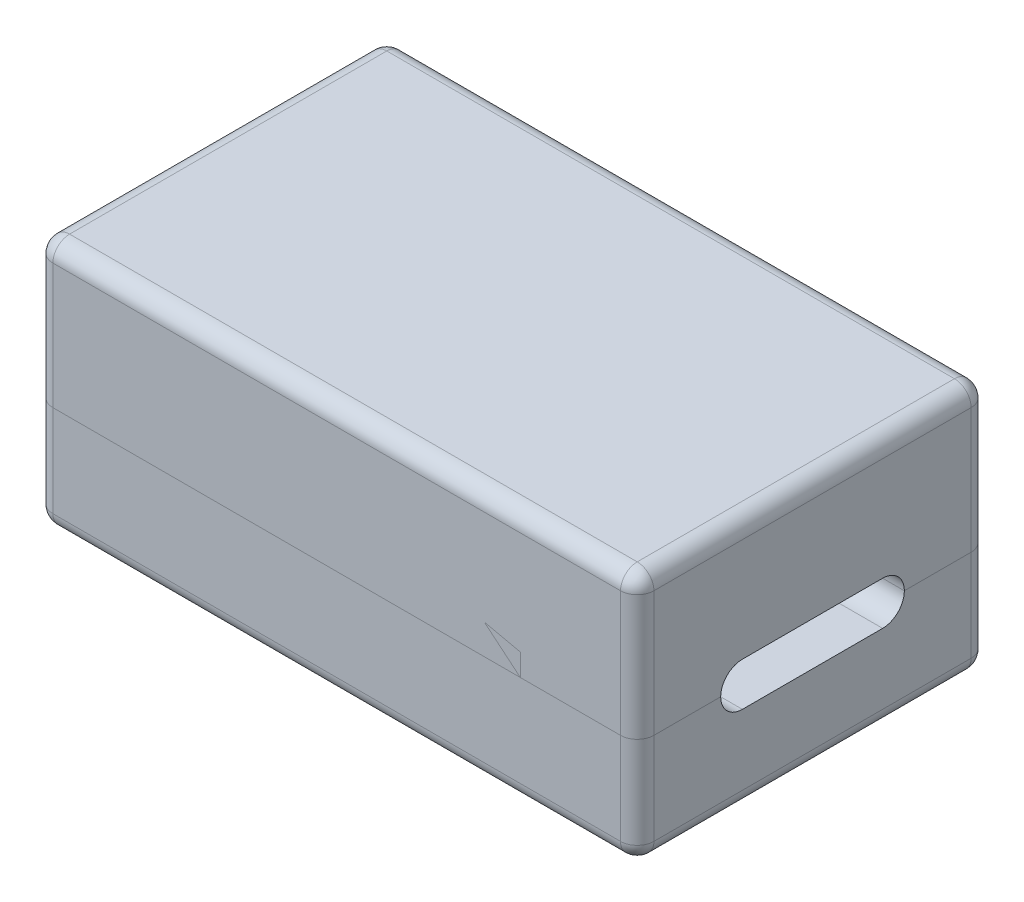
SolidWorks part; units mm, degrees
ref_plane "Front Plane" through (0, 0, 0) normal (0, 0, 1) x (1, 0, 0)
ref_plane "Top Plane" through (0, 0, 0) normal (0, 1, 0) x (1, 0, 0)
ref_plane "Right Plane" through (0, 0, 0) normal (1, 0, 0) x (0, 0, -1)
sketch "Sketch1" plane through (0, 0, 0) normal (0, 1, 0) x (1, 0, 0)
  line L1 (-18, 10.5) -> (18, 10.5)
  line L2 (-18, 10.5) -> (-18, -10.5)
  line L3 (-18, -10.5) -> (18, -10.5)
  line L4 (18, 10.5) -> (18, -10.5)
  line L5 (-18, 10.5) -> (18, -10.5) construction
  line L6 (-18, -10.5) -> (18, 10.5) construction
  point P0 (0, 0)
  dimension "D1" = 21
  dimension "D2" = 36
extrude "Boss-Extrude2" add sketch "Sketch1" along normal blind 15
sketch "Sketch2" plane through (18, 0, 0) normal (1, 0, 0) x (0, 0, -1)
  line L0 (-4.2, 6.5) -> (4.2, 6.5) construction
  line L1 (-4.2, 7.8) -> (4.2, 7.8)
  line L2 (-4.2, 5.2) -> (4.2, 5.2)
  line L4 (10.5, 15) -> (10.5, 0) construction
  line L5 (-10.5, 0) -> (10.5, 0) construction
  arc A0 (-4.2, 7.8) -> (-4.2, 5.2) centre (-4.2, 6.5) ccw
  arc A1 (4.2, 5.2) -> (4.2, 7.8) centre (4.2, 6.5) ccw
  point P2 (0, 6.5)
  dimension "D1" = 10.5
  dimension "D2" = 6.5
  dimension "D3" = 8.4
  dimension "D4" = 1.3
extrude "Cut-Extrude1" cut sketch "Sketch2" against normal blind 15
ref_plane "Plane2" through (0, 6.5, 0) normal (0, 1, 0) x (1, 0, 0)
split "Split1" trim tools "Plane2" bodies to split 103 resulting bodies 104 105
sketch "Sketch5" plane through (0, 6.5, 0) normal (0, 1, 0) x (1, 0, 0)
  line L0 (-18, 10.5) -> (-18, -10.5) construction
  line L1 (-15, 7.5) -> (15, 7.5)
  line L2 (-15, 7.5) -> (-15, -7.5)
  line L3 (-15, -7.5) -> (15, -7.5)
  line L4 (15, 7.5) -> (15, -7.5)
  line L5 (18, 5.5) -> (18, 10.5) construction
  line L6 (18, 10.5) -> (-18, 10.5) construction
  line L7 (-18, -10.5) -> (18, -10.5) construction
  dimension "D1" = 3
  dimension "D2" = 3
  dimension "D3" = 3
  dimension "D4" = 3
extrude "Cut-Extrude2" cut sketch "Sketch5" against normal blind 3.5
sketch "Sketch7" plane through (0, 6.5, 0) normal (0, -1, 0) x (1, 0, 0)
  line L0 (-18, -10.5) -> (-18, 10.5) construction
  line L1 (-15, 7.5) -> (15, 7.5)
  line L2 (-15, 7.5) -> (-15, -7.5)
  line L3 (-15, -7.5) -> (15, -7.5)
  line L4 (15, 7.5) -> (15, -7.5)
  line L5 (18, 10.5) -> (18, 5.5) construction
  line L6 (-18, 10.5) -> (18, 10.5) construction
  line L7 (18, -10.5) -> (-18, -10.5) construction
  dimension "D1" = 3
  dimension "D2" = 3
  dimension "D3" = 3
  dimension "D4" = 3
extrude "Cut-Extrude3" cut sketch "Sketch7" against normal blind 5.5
fillet "Fillet1" radius 1 8 edges at (-18, 10.75, -10.5) (-18, 10.75, 10.5) (18, 10.75, 10.5) (18, 10.75, -10.5) (-18, 15, 0) (0, 15, 10.5) (18, 15, 0) (0, 15, -10.5)
fillet "Fillet2" radius 1 8 edges at (18, 3.25, 10.5) (18, 3.25, -10.5) (18, 0, 0) (0, 0, -10.5) (-18, 3.25, -10.5) (-18, 0, 0) (0, 0, 10.5) (-18, 3.25, 10.5)
sketch "Sketch9" plane through (0, 0, 10.5) normal (0, 0, 1) x (1, 0, 0)
  line L0 (0, 0) -> (0, 10.1823) construction
  line L1 (11.55, 6.5) -> (-11.55, 6.5) construction
  line L2 (-11, 6.5) -> (-8, 6.5)
  line L3 (-11, 6.5) -> (-11, 9.5)
  line L4 (-11, 9.5) -> (-8, 9.5)
  line L5 (-8, 6.5) -> (-8, 9.5)
  line L6 (11, 6.5) -> (11, 9.5)
  line L7 (8, 6.5) -> (8, 9.5)
  line L8 (11, 9.5) -> (8, 9.5)
  line M7 (17, 6.5) -> (-17, 6.5)
  dimension "D1" = 3
  dimension "D2" = 8
  dimension "D3" = 0
  dimension "D4" = 3
extrude "Boss-Extrude3" add sketch "Sketch9" against normal blind 1 contours L5 L4 L3 L2
extrude "Boss-Extrude4" add sketch "Sketch9<4>" against normal blind 1 contours L6 L8 L7 M7 region at (9.5, 8, 10.5)
sketch "Sketch9<4>" plane through (0, 0, 10.5) normal (0, 0, 1) x (1, 0, 0) same geometry as "Sketch9"
sketch "Sketch10" plane through (0, 0, 9.5) normal (0, 0, -1) x (-1, 0, 0)
  line L0 (-8, 6.5) -> (-8, 9.5) construction
  line L1 (-11, 9.5) -> (-8, 9.5)
  line L2 (-11, 9.5) -> (-11, 8)
  line L3 (-11, 8) -> (-8, 8)
  line L4 (-8, 9.5) -> (-8, 8)
  line L5 (8, 6.5) -> (8, 9.5) construction
  line L6 (8, 9.5) -> (11, 9.5)
  line L7 (8, 9.5) -> (8, 8)
  line L8 (8, 8) -> (11, 8)
  line L9 (11, 9.5) -> (11, 8)
  line L10 (11, 6.5) -> (11, 9.5) construction
extrude "Boss-Extrude5" add sketch "Sketch10" along normal blind 1
sketch "Sketch11" plane through (11, 0, 0) normal (1, 0, 0) x (0, 0, -1)
  line L0 (-9.5, 9.5) -> (-8.5, 8)
  line L1 (-8.5, 9.5) -> (-10.5, 9.5) construction
  line L2 (-8.5, 9.5) -> (-8.5, 8) construction
  line L3 (-8.5, 8) -> (-8.5, 9.5)
  line L4 (-8.5, 9.5) -> (-9.5, 9.5)
extrude "Cut-Extrude4" cut sketch "Sketch11" against normal through all
sketch "Sketch12" plane through (0, 0, -10.5) normal (0, 0, -1) x (-1, 0, 0)
  line L0 (0, 0) -> (0, 15.2889) construction
  line L1 (11.55, 6.5) -> (-11.55, 6.5) construction
  line L2 (-1.5, 9.5) -> (1.5, 9.5)
  line L3 (-1.5, 9.5) -> (-1.5, 3.5)
  line L4 (-1.5, 3.5) -> (1.5, 3.5)
  line L5 (1.5, 9.5) -> (1.5, 3.5)
  line L6 (-1.5, 9.5) -> (1.5, 3.5) construction
  line L7 (-1.5, 3.5) -> (1.5, 9.5) construction
  point P1 (0, 6.5)
  dimension "D1" = 6
  dimension "D2" = 3
extrude "Boss-Extrude6" add sketch "Sketch12" along normal mid plane 1
fillet "Fillet3" radius 11 1 edges at (0, 3.5, -11)
fillet "Fillet4" radius 0.5 4 edges at (9.5, 9.5, 9.5) (-9.5, 9.5, 9.5) (-9.5, 9.5, 10.5) (9.5, 9.5, 10.5)
sketch "Sketch17" plane through (0, 0, -10) normal (0, 0, 1) x (1, 0, 0)
  line L1 (-1.5, 9.5) -> (1.5, 9.5)
  line L2 (-1.5, 9.5) -> (-1.5, 11.5)
  line L3 (-1.5, 11.5) -> (1.5, 11.5)
  line L4 (1.5, 9.5) -> (1.5, 11.5)
  dimension "D1" = 3
  dimension "D2" = 2
extrude "Boss-Extrude7" add sketch "Sketch17" against normal blind 1
sketch "Sketch18" plane through (0, 0, -10) normal (0, 0, 1) x (1, 0, 0)
  line L0 (-1.5, 6.5) -> (-1.5, 11.5) construction
  line L1 (-1.5, 10) -> (1.5, 10)
  line L2 (-1.5, 10) -> (-1.5, 8.5)
  line L3 (-1.5, 8.5) -> (1.5, 8.5)
  line L4 (1.5, 10) -> (1.5, 8.5)
  line L5 (1.5, 11.5) -> (1.5, 6.5) construction
  line L6 (11.825, 6.5) -> (-11.825, 6.5) construction
  dimension "D1" = 1.5
  dimension "D2" = 2
extrude "Boss-Extrude8" add sketch "Sketch18" along normal blind 1
fillet "Fillet5" radius 0.75 2 edges at (0, 8.5, -9) (0, 10, -9)
fillet "Fillet6" radius 1 1 edges at (0, 11.5, -10) conic radius 10
